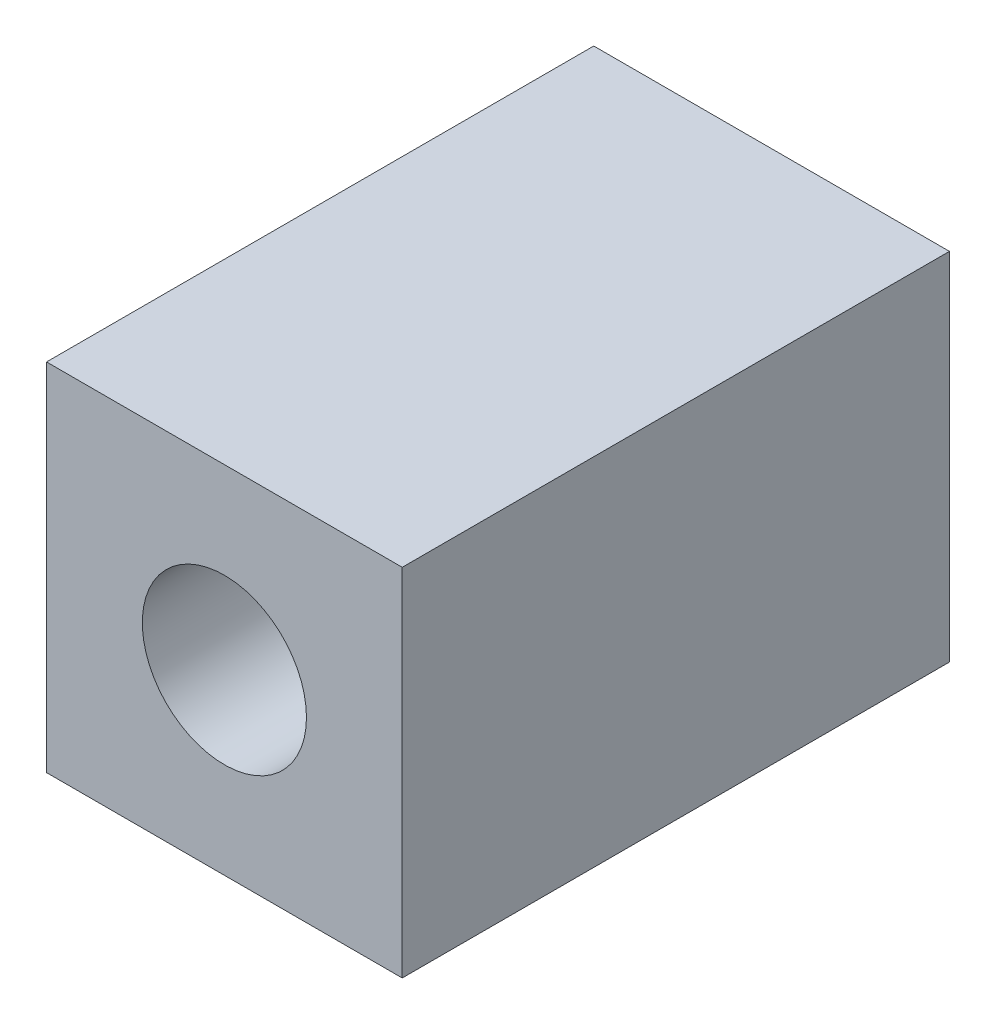
SolidWorks part; units mm, degrees
ref_plane "정면" through (0, 0, 0) normal (0, 0, 1) x (1, 0, 0)
ref_plane "윗면" through (0, 0, 0) normal (0, 1, 0) x (1, 0, 0)
ref_plane "우측면" through (0, 0, 0) normal (1, 0, 0) x (0, 0, -1)
ref_axis "기준축2" through (0, 0, 210) along (0, 0, -1)
ref_axis "기준축4" through (0, 55, 0) along (0, -1, 0)
sketch "스케치1" plane through (0, 0, 0) normal (0, 0, 1) x (1, 0, 0)
  circle A0 centre (0, 0) radius 25
  dimension "D1" = 50
extrude "보스-돌출1" [suppressed] add sketch "스케치1" along normal blind 200
sketch "스케치2" plane through (0, 0, 0) normal (0, 0, 1) x (1, 0, 0)
  line L1 (-65, 65) -> (65, 65)
  line L2 (-65, 65) -> (-65, -65)
  line L3 (-65, -65) -> (65, -65)
  line L4 (65, 65) -> (65, -65)
  circle A0 centre (0, 0) radius 30
  point P4 (0, 65)
  point P6 (65, 0)
  dimension "D3" = 60
  dimension "D1" = 130
  dimension "D2" = 130
extrude "보스-돌출2" add sketch "스케치2" along normal blind 200 separate body
